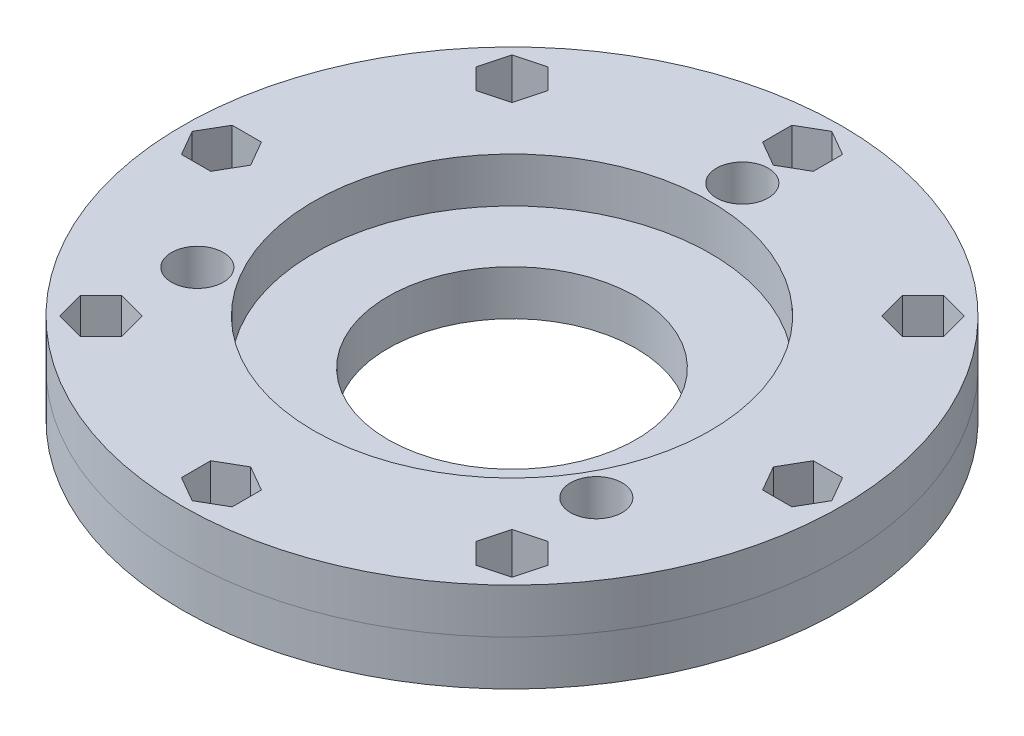
SolidWorks part; units mm, degrees
ref_plane "Front Plane" through (0, 0, 0) normal (0, 0, 1) x (1, 0, 0)
ref_plane "Top Plane" through (0, 0, 0) normal (0, 1, 0) x (1, 0, 0)
ref_plane "Right Plane" through (0, 0, 0) normal (1, 0, 0) x (0, 0, -1)
sketch "Sketch1" plane through (0, 0, 0) normal (0, 1, 0) x (1, 0, 0)
  circle A0 centre (0, 0) radius 46.5
  circle A1 centre (0, 0) radius 32.5 construction
  circle A2 centre (0, 32.5) radius 2.25
  circle A3 centre (28.1458, -16.25) radius 2.25
  circle A4 centre (-28.1458, -16.25) radius 2.25
  circle A5 centre (0, 0) radius 17.5
  point P13 (0, 0)
  dimension "D1" = 93
  dimension "D2" = 65
  dimension "D3" = 4.5
  dimension "D5" = 35
  dimension "D4" = 3
extrude "Boss-Extrude1" add sketch "Sketch1" along normal blind 12.7
sketch "Sketch2" plane through (0, 12.7, 0) normal (0, 1, 0) x (1, 0, 0)
  circle A0 centre (0, 0) radius 28
  dimension "D1" = 56
extrude "Cut-Extrude1" cut sketch "Sketch2" against normal blind 6.35
sketch "Sketch3" plane through (0, 12.7, 0) normal (0, 1, 0) x (1, 0, 0)
  line L0 (0, 41) -> (0, 0) construction
  circle A0 centre (0, 0) radius 41 construction
  circle A1 centre (0, 41) radius 2.5
  circle A2 centre (28.9914, 28.9914) radius 2.5
  circle A3 centre (41, 0) radius 2.5
  circle A4 centre (28.9914, -28.9914) radius 2.5
  circle A5 centre (0, -41) radius 2.5
  circle A6 centre (-28.9914, -28.9914) radius 2.5
  circle A7 centre (-41, 0) radius 2.5
  circle A8 centre (-28.9914, 28.9914) radius 2.5
  point P21 (0, 0)
  dimension "D1" = 82
  dimension "D2" = 5
  dimension "D3" = 8
extrude "Cut-Extrude2" cut sketch "Sketch3" against normal blind 6.35
sketch "Sketch4" plane through (0, 12.7, 0) normal (0, 1, 0) x (1, 0, 0)
  line L0 (0, 45.1281) -> (-3.575, 43.064)
  line L1 (-3.575, 43.064) -> (-3.575, 38.936)
  line L2 (-3.575, 38.936) -> (0, 36.8719)
  line L3 (0, 36.8719) -> (3.575, 38.936)
  line L4 (3.575, 38.936) -> (3.575, 43.064)
  line L5 (3.575, 43.064) -> (0, 45.1281)
  line L6 (0, 45.1281) -> (0, 36.8719) construction
  line L7 (32.9788, 27.923) -> (31.9104, 31.9104)
  line L8 (31.9104, 31.9104) -> (27.923, 32.9788)
  line L9 (27.923, 32.9788) -> (25.004, 30.0598)
  line L10 (25.004, 30.0598) -> (26.0724, 26.0724)
  line L11 (26.0724, 26.0724) -> (30.0598, 25.004)
  line L12 (30.0598, 25.004) -> (32.9788, 27.923)
  line L13 (43.064, -3.575) -> (45.1281, 0)
  line L14 (45.1281, 0) -> (43.064, 3.575)
  line L15 (43.064, 3.575) -> (38.936, 3.575)
  line L16 (38.936, 3.575) -> (36.8719, 0)
  line L17 (36.8719, 0) -> (38.936, -3.575)
  line L18 (38.936, -3.575) -> (43.064, -3.575)
  line L19 (27.923, -32.9788) -> (31.9104, -31.9104)
  line L20 (31.9104, -31.9104) -> (32.9788, -27.923)
  line L21 (32.9788, -27.923) -> (30.0598, -25.004)
  line L22 (30.0598, -25.004) -> (26.0724, -26.0724)
  line L23 (26.0724, -26.0724) -> (25.004, -30.0598)
  line L24 (25.004, -30.0598) -> (27.923, -32.9788)
  line L25 (-3.575, -43.064) -> (0, -45.1281)
  line L26 (0, -45.1281) -> (3.575, -43.064)
  line L27 (3.575, -43.064) -> (3.575, -38.936)
  line L28 (3.575, -38.936) -> (0, -36.8719)
  line L29 (0, -36.8719) -> (-3.575, -38.936)
  line L30 (-3.575, -38.936) -> (-3.575, -43.064)
  line L31 (-32.9788, -27.923) -> (-31.9104, -31.9104)
  line L32 (-31.9104, -31.9104) -> (-27.923, -32.9788)
  line L33 (-27.923, -32.9788) -> (-25.004, -30.0598)
  line L34 (-25.004, -30.0598) -> (-26.0724, -26.0724)
  line L35 (-26.0724, -26.0724) -> (-30.0598, -25.004)
  line L36 (-30.0598, -25.004) -> (-32.9788, -27.923)
  line L37 (-43.064, 3.575) -> (-45.1281, 0)
  line L38 (-45.1281, 0) -> (-43.064, -3.575)
  line L39 (-43.064, -3.575) -> (-38.936, -3.575)
  line L40 (-38.936, -3.575) -> (-36.8719, 0)
  line L41 (-36.8719, 0) -> (-38.936, 3.575)
  line L42 (-38.936, 3.575) -> (-43.064, 3.575)
  line L43 (-27.923, 32.9788) -> (-31.9104, 31.9104)
  line L44 (-31.9104, 31.9104) -> (-32.9788, 27.923)
  line L45 (-32.9788, 27.923) -> (-30.0598, 25.004)
  line L46 (-30.0598, 25.004) -> (-26.0724, 26.0724)
  line L47 (-26.0724, 26.0724) -> (-25.004, 30.0598)
  line L48 (-25.004, 30.0598) -> (-27.923, 32.9788)
  line L49 (-30.0598, 25.004) -> (-27.923, 32.9788) construction
  circle A0 centre (0, 32.5) radius 3.65
  circle A1 centre (28.1458, -16.25) radius 3.65
  circle A2 centre (-28.1458, -16.25) radius 3.65
  circle A3 centre (-28.1458, -16.25) radius 2.25 construction
  circle A4 centre (0, 41) radius 2.5 construction
  circle A5 centre (0, 41) radius 2.5 construction
  circle A6 centre (-28.9914, 28.9914) radius 2.5 construction
  circle A7 centre (-28.9914, 28.9914) radius 2.5 construction
  point P9 (0, 0)
  point P64 (0, 0)
  dimension "D1" = 3
  dimension "8" = 7.3
  dimension "7.15" = 7.15
  dimension "D3" = 120
  dimension "D4" = 120
  dimension "D5" = 8
extrude "Cut-Extrude3" cut sketch "Sketch4" against normal blind 6.35
sketch "Sketch5" plane through (0, 12.7, 0) normal (0, 1, 0) x (1, 0, 0)
  line L2 (0, 36.8719) -> (0, 45.1281) construction
  circle A0 centre (0, 41) radius 2.5 construction
  circle A1 centre (0, 32.5) radius 2.25 construction
  circle A2 centre (0, 32.5) radius 2.25 construction
  dimension "D1" = 5
split "Split1" bodies to split 105 resulting bodies 106 107 split by face at (0, 6.35, 17.5)
